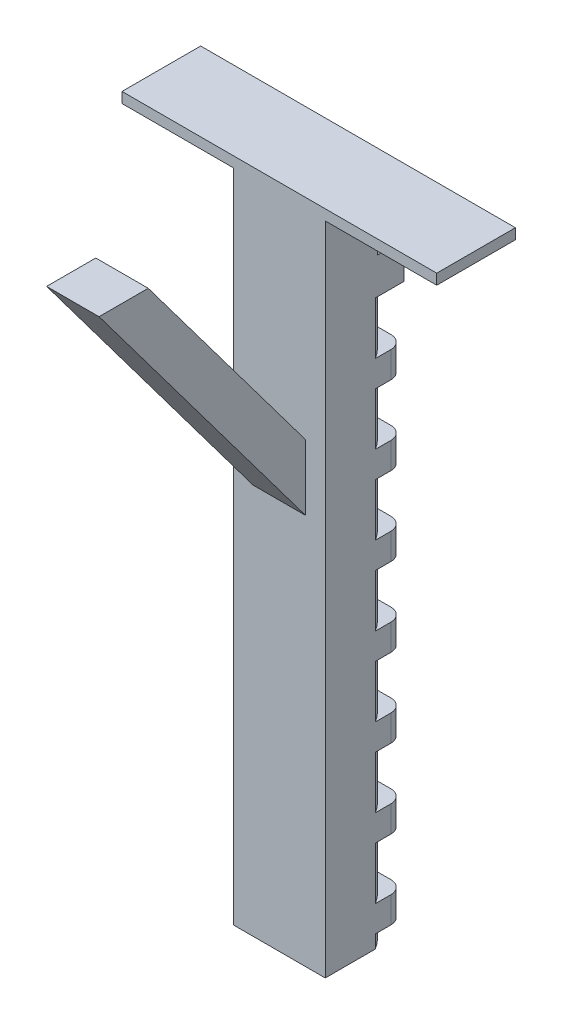
SolidWorks part; units mm, degrees
ref_plane "Front Plane" through (0, 0, 0) normal (0, 0, 1) x (1, 0, 0)
ref_plane "Top Plane" through (0, 0, 0) normal (0, 1, 0) x (1, 0, 0)
ref_plane "Right Plane" through (0, 0, 0) normal (1, 0, 0) x (0, 0, -1)
sketch "Sketch1" plane through (0, 0, 0) normal (0, 0, 1) x (1, 0, 0)
  line L1 (-17.5, 125) -> (17.5, 125)
  line L2 (-17.5, 125) -> (-17.5, -125)
  line L3 (-17.5, -125) -> (17.5, -125)
  line L4 (17.5, 125) -> (17.5, -125)
  line L5 (-17.5, 125) -> (17.5, -125) construction
  line L6 (-17.5, -125) -> (17.5, 125) construction
  point P0 (0, 0)
  dimension "D1" = 35
  dimension "D2" = 250
extrude "Boss-Extrude1" add sketch "Sketch1" along normal blind 30
sketch "Sketch2" plane through (0, 0, 0) normal (0, 0, 1) x (1, 0, 0)
  line L0 (17.5, 125) -> (-17.5, 125) construction
  line L1 (-60, 129) -> (60, 129)
  line L2 (-60, 129) -> (-60, 125)
  line L3 (-60, 125) -> (60, 125)
  line L4 (60, 129) -> (60, 125)
  line L5 (-60, 129) -> (60, 125) construction
  line L6 (-60, 125) -> (60, 129) construction
  line L7 (0, 127) -> (0, 0) construction
  point P0 (0, 127)
  dimension "D1" = 4
  dimension "D2" = 120
extrude "Boss-Extrude2" add sketch "Sketch2" along normal blind 30
sketch "Sketch4" plane through (0, 0, 0) normal (0, 0, 1) x (1, 0, 0)
  line L0 (-38.75, 125) -> (-17.5, 103.75)
  line L1 (-60, 125) -> (-17.5, 125) construction
  line L2 (-17.5, 125) -> (-17.5, -125) construction
  line L3 (-17.5, 103.75) -> (-17.5, 125)
  line L4 (-17.5, 125) -> (-38.75, 125)
  line L5 (38.75, 125) -> (17.5, 125)
  line L6 (17.5, 125) -> (60, 125) construction
  line L7 (17.5, 125) -> (17.5, 103.75)
  line L8 (17.5, -125) -> (17.5, 125) construction
  line L9 (17.5, 103.75) -> (38.75, 125)
  line L10 (17.5, 103.75) -> (-17.5, 103.75) construction
extrude "Boss-Extrude3" add sketch "Sketch4" along normal blind 10
sketch "Sketch5" plane through (0, 0, 0) normal (0, 1, 0) x (1, 0, 0)
  line L0 (17.5, -10.9183) -> (-17.5, -10.9183) construction
  line L4 (17.5, 0) -> (-17.5, 0)
  line L5 (17.5, -30) -> (17.5, 0)
  line L6 (-17.5, -30) -> (17.5, -30)
  line L7 (-17.5, 0) -> (-17.5, -30)
  line L8 (17.5, 0) -> (-17.5, 0)
  line L9 (17.5, -10.9183) -> (17.5, 0)
  line L11 (-17.5, 0) -> (-17.5, -10.9183)
  arc A0 (17.5, -10.9183) -> (-17.5, -10.9183) centre (0, -21.4749) ccw
  dimension "D1" = 0
extrude "Cut-Extrude1" cut sketch "Sketch5" against normal blind 20
pattern_linear "LPattern1" count 5 spacing 30 along (0, -1, 0) count 4 spacing 30 along (0, 1, 0) of "Cut-Extrude1"
fillet "Fillet1" radius 5 14 edges at (-17.5, 65, 0) (17.5, 65, 0) (17.5, 35, 0) (17.5, 5, 0) (17.5, -25, 0) (17.5, -55, 0) (17.5, -85, 0) (17.5, -115, 0) (-17.5, 35, 0) (-17.5, 5, 0) (-17.5, -25, 0) (-17.5, -55, 0) (-17.5, -85, 0) (-17.5, -115, 0)
sketch "Sketch6" plane through (0, 0, 0) normal (1, 0, 0) x (0, 0, -1)
  line L0 (-30, 49) -> (-90, 129)
  line L1 (-30, -125) -> (-30, 125) construction
  line L2 (-90, 129) -> (-30, 129) construction
  line L3 (-30, 24) -> (-108.75, 129)
  line L4 (-108.75, 129) -> (-90, 129)
  line L5 (-30, 49) -> (-30, 24)
  dimension "D1" = 60
  dimension "D2" = 80
  dimension "D3" = 15
extrude "Boss-Extrude4" add sketch "Sketch6" along normal blind 10 and the other way blind 10
